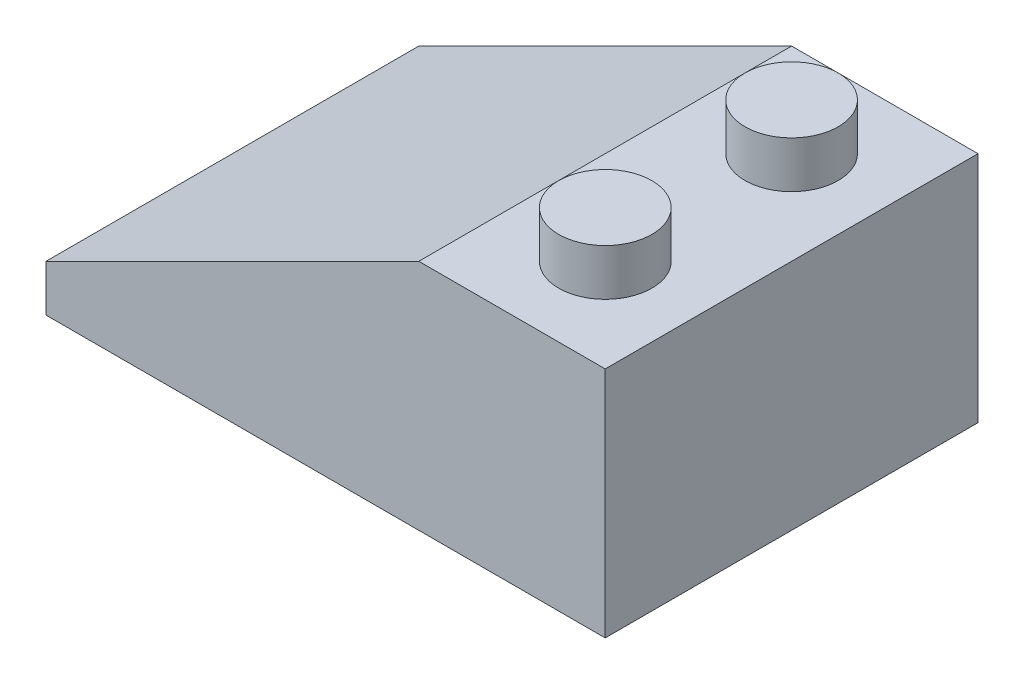
SolidWorks part; units mm, degrees
ref_plane "Front Plane" through (0, 0, 0) normal (0, 0, 1) x (1, 0, 0)
ref_plane "Top Plane" through (0, 0, 0) normal (0, 1, 0) x (1, 0, 0)
ref_plane "Right Plane" through (0, 0, 0) normal (1, 0, 0) x (0, 0, -1)
sketch "Sketch2" plane through (0, 0, 0) normal (0, 0, 1) x (1, 0, 0)
  line L0 (0, 0) -> (-24, 0)
  line L1 (0, 0) -> (0, 10)
  line L2 (0, 10) -> (-8, 10)
  line L3 (-24, 0) -> (-24, 2)
  line L4 (-24, 2) -> (-8, 10)
  dimension "D1" = 24
  dimension "D2" = 2
  dimension "D3" = 8
  dimension "D4" = 10
extrude "Boss-Extrude1" add sketch "Sketch2" along normal blind 8 and the other way blind 8
sketch "Sketch3" plane through (0, 10, 0) normal (0, 1, 0) x (1, 0, 0)
  line L0 (0, -8) -> (-8, -8) construction
  line L2 (-8, 8) -> (-8, -8) construction
  line L3 (0, 0) -> (-9.1006, 0) construction
  line L4 (-9.1006, 0) -> (-9.1404, 0.139) construction
  line L5 (0, 8) -> (-8, 8) construction
  line L7 (0, 8) -> (0, -8) construction
  circle A0 centre (-3.9964, -4) radius 2
  circle A1 centre (-4, 4) radius 2
  point P4 (-4, -8)
  dimension "D3" = 4
  dimension "D5" = 4
  dimension "D1" = 4.0036
  dimension "D2" = 4
  dimension "D4" = 4
extrude "Boss-Extrude2" add sketch "Sketch3" along normal blind 2
shell "Shell1" thickness 1 removed face at (-12, 0, 0)
sketch "Sketch4" plane through (0, 0, 0) normal (0, -1, 0) x (1, 0, 0)
  line L0 (-12, 7) -> (-12, -8) construction
  line L1 (-23, 7) -> (-1, 7) construction
  line L2 (-24, -8) -> (0, -8) construction
  circle A0 centre (-8, 0) radius 2.7
  circle A1 centre (-16, 0) radius 1.7
  circle A3 centre (-16, 0) radius 2.7
  circle A4 centre (-8, 0) radius 1.7
  dimension "D1" = 5.4
  dimension "D5" = 1
  dimension "D2" = 8
  dimension "D3" = 1
extrude "Boss-Extrude3" add sketch "Sketch4" against normal up to next
